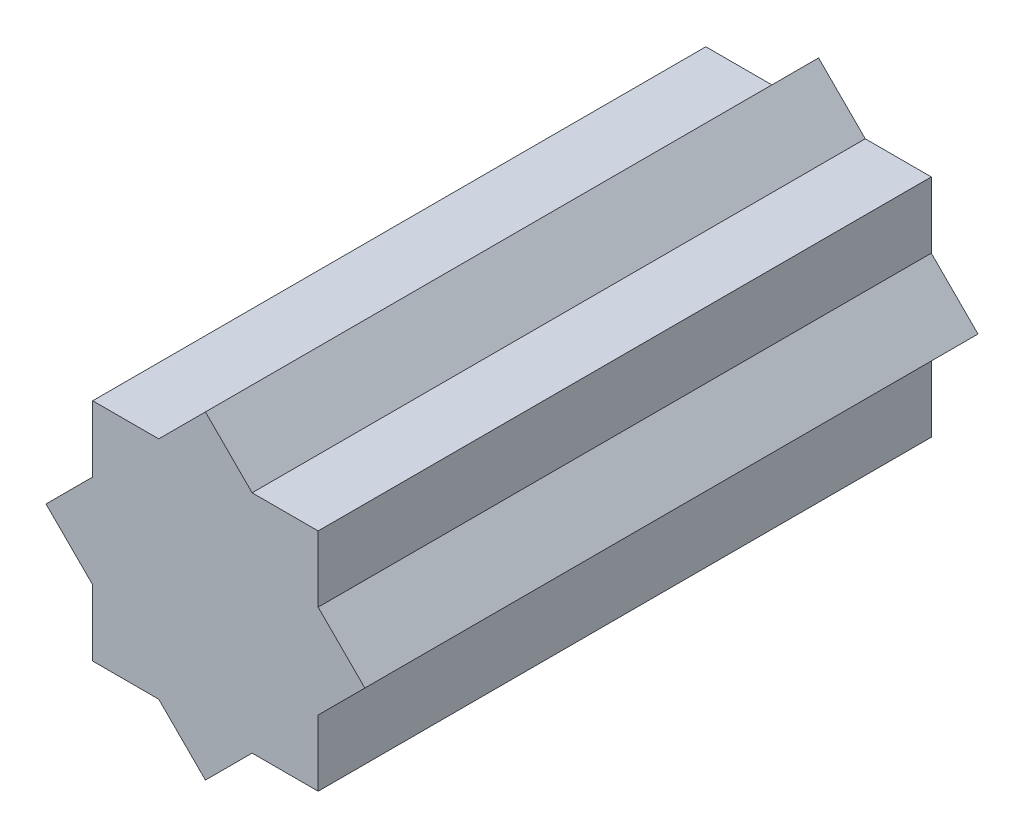
SolidWorks part; units mm, degrees
ref_plane "Front Plane" through (0, 0, 0) normal (0, 0, 1) x (1, 0, 0)
ref_plane "Top Plane" through (0, 0, 0) normal (0, 1, 0) x (1, 0, 0)
ref_plane "Right Plane" through (0, 0, 0) normal (1, 0, 0) x (0, 0, -1)
sketch "Sketch1" plane through (0, 0, 0) normal (0, 0, 1) x (1, 0, 0)
  line L0 (0, 3.9) -> (1.1423, 2.7577)
  line L1 (0, 3.9) -> (-1.1423, 2.7577)
  line L2 (3.9, 0) -> (2.7577, -1.1423)
  line L3 (-3.9, 0) -> (-2.7577, -1.1423)
  line L4 (-2.7577, 2.7577) -> (0, 0) construction
  line L5 (-2.7577, 2.7577) -> (-1.1423, 2.7577)
  line L6 (-2.7577, 2.7577) -> (-2.7577, 1.1423)
  line L7 (-2.7577, -2.7577) -> (-1.1423, -2.7577)
  line L8 (0, 0) -> (0, 10.0133) construction
  line L9 (2.7577, 2.7577) -> (2.7577, 1.1423)
  line L10 (20.7795, 0) -> (-15.3587, 0) construction
  line L11 (0, 0) -> (2.7577, 2.7577) construction
  line L12 (2.7577, -2.7577) -> (0, 0) construction
  line L13 (0, 0) -> (-2.7577, -2.7577) construction
  line L14 (-2.7577, -1.1423) -> (-2.7577, -2.7577)
  line L15 (-2.7577, 1.1423) -> (-3.9, 0)
  line L16 (1.1423, 2.7577) -> (2.7577, 2.7577)
  line L17 (2.7577, 1.1423) -> (3.9, 0)
  line L18 (2.7577, -1.1423) -> (2.7577, -2.7577)
  line L19 (1.1423, -2.7577) -> (0, -3.9)
  line L20 (-1.1423, -2.7577) -> (0, -3.9)
  line L21 (1.1423, -2.7577) -> (2.7577, -2.7577)
  dimension "D1" = 3.9
extrude "Boss-Extrude1" add sketch "Sketch1" along normal blind 7.5 and the other way blind 7.5
